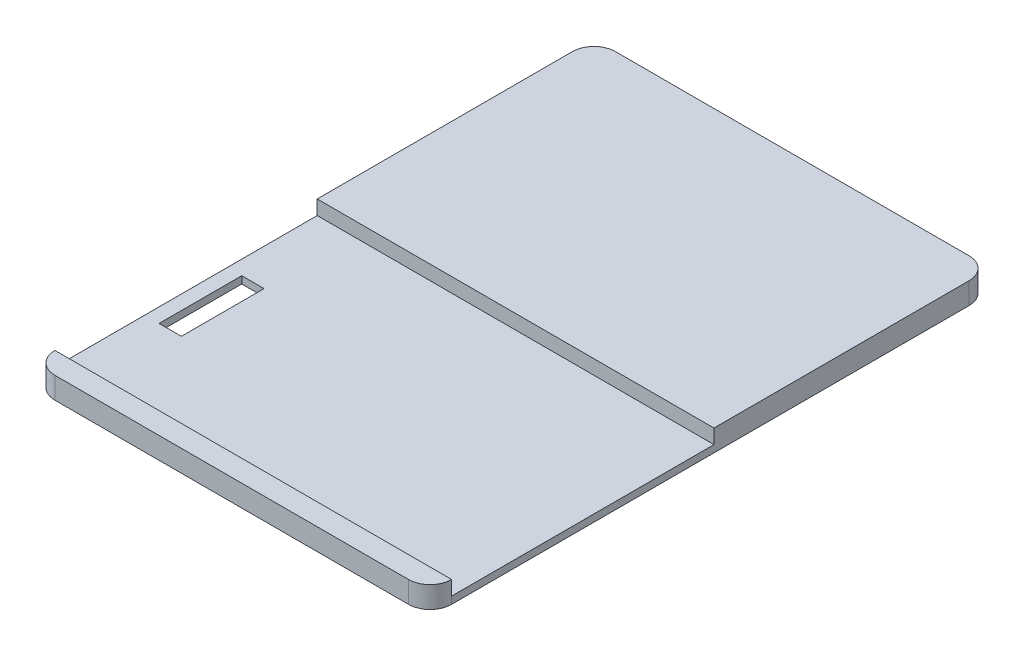
SolidWorks part; units mm, degrees
material "PMMA"
ref_plane "Front Plane" through (0, 0, 0) normal (0, 0, 1) x (1, 0, 0)
ref_plane "Top Plane" through (0, 0, 0) normal (0, 1, 0) x (1, 0, 0)
ref_plane "Right Plane" through (0, 0, 0) normal (1, 0, 0) x (0, 0, -1)
sketch "Sketch1" plane through (0, 0, 0) normal (0, 1, 0) x (1, 0, 0)
  line L0 (0, 51.4541) -> (0, -51.759) construction
  line L1 (-52.1402, 0) -> (52.1402, 0) construction
  line L2 (0, -17.75) -> (25.0802, -17.75) construction
  line L3 (-24.6, -39) -> (24.6, -39)
  line L4 (-27.6, -36) -> (-27.6, 36)
  line L5 (-24.6, 39) -> (24.6, 39)
  line L6 (27.6, -36) -> (27.6, 36)
  line L7 (-27.6, -39) -> (27.6, 39) construction
  line L8 (-27.6, 39) -> (27.6, -39) construction
  line L9 (-27.6, -36) -> (27.6, -36)
  line L10 (-27.6, -36) -> (-27.6, 0.5)
  line L11 (-27.6, 0.5) -> (27.6, 0.5)
  line L12 (27.6, -36) -> (27.6, 0.5)
  line L13 (-27.6, -36) -> (27.6, 0.5) construction
  line L14 (-27.6, 0.5) -> (27.6, -36) construction
  line L18 (-22.5, -12) -> (-25.6, -12)
  line L19 (-22.5, -12) -> (-22.5, -23.5)
  line L20 (-22.5, -23.5) -> (-25.6, -23.5)
  line L21 (-25.6, -12) -> (-25.6, -23.5)
  arc A0 (27.6, 36) -> (24.6, 39) centre (24.6, 36) ccw
  arc A1 (27.6, -36) -> (24.6, -39) centre (24.6, -36) cw
  arc A2 (-24.6, -39) -> (-27.6, -36) centre (-24.6, -36) cw
  arc A3 (-24.6, 39) -> (-27.6, 36) centre (-24.6, 36) ccw
  point P5 (0, 0)
  point P11 (0, -17.75)
  dimension "D10" = 3
  dimension "D1" = 78
  dimension "D2" = 55.2
  dimension "D3" = 55.2
  dimension "D4" = 36.5
  dimension "D5" = 3
  dimension "D6" = 11.5
  dimension "D7" = 3.1
  dimension "D8" = 2
  dimension "D9" = 3
extrude "Boss-Extrude1" add sketch "Sketch1" along normal blind 3 contours A2 L3 A1 L9 | L5 A3 L4 L11 L6 A0 region at (0, 0, 37.4802) region at (0, 0, -19.7162)
extrude "Boss-Extrude2" add sketch "Sketch1<5>" along normal blind 1 contours L11 L4 L9 L6 L21 L18 L19 L20 region at (0.4332, 0, 17.75)
sketch "Sketch1<5>" plane through (0, 0, 0) normal (0, 1, 0) x (1, 0, 0) same geometry as "Sketch1"
